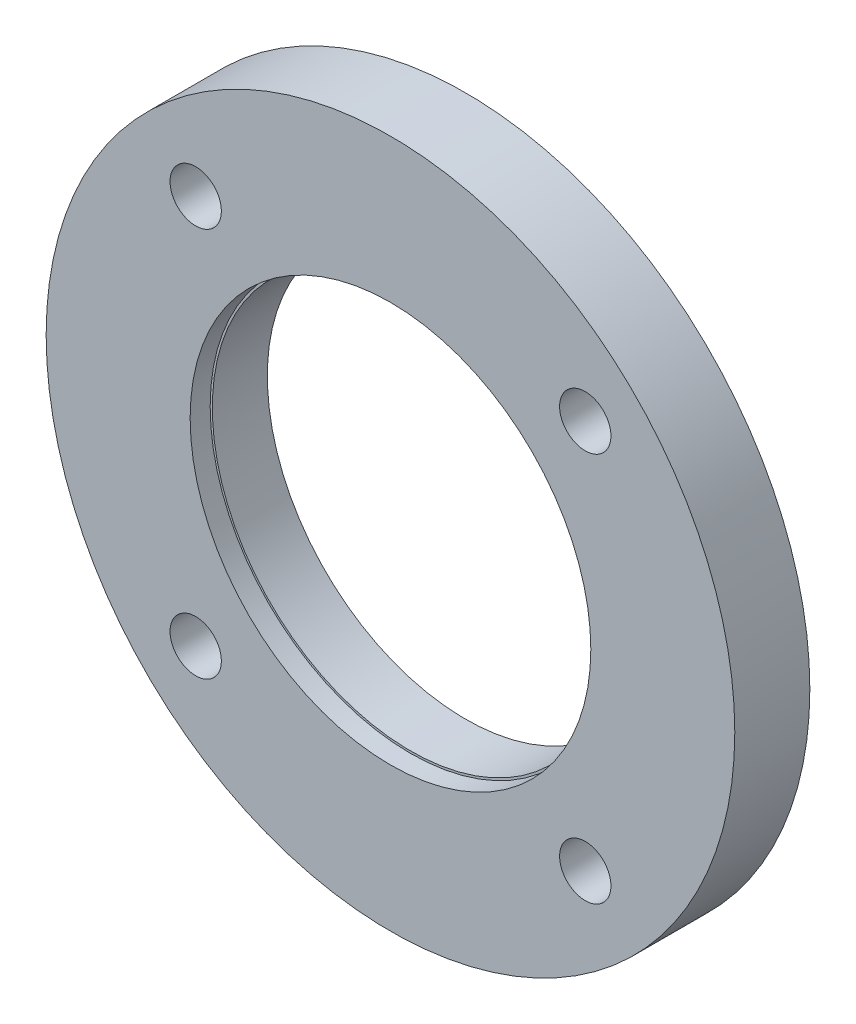
SolidWorks part; units mm, degrees
ref_plane "Front Plane" through (0, 0, 0) normal (0, 0, 1) x (1, 0, 0)
ref_plane "Top Plane" through (0, 0, 0) normal (0, 1, 0) x (1, 0, 0)
ref_plane "Right Plane" through (0, 0, 0) normal (1, 0, 0) x (0, 0, -1)
ref_axis "Z" through (0, 0, -0.1647) along (0, 0, 1)
sketch "Sketch1" plane through (0, 0, 0) normal (0, 1, 0) x (1, 0, 0)
  line L0 (-15.83, 0) -> (-27.5, 0)
  line L1 (-27.5, 0) -> (-27.5, -5.994)
  line L2 (-27.5, -5.994) -> (-16, -5.994)
  line L3 (-16, -5.994) -> (-16, -4.394)
  line L4 (-16, -4.394) -> (-15.83, -4.394)
  line L5 (-15.83, -4.394) -> (-15.83, 0)
  line L6 (0, -1.0245) -> (0, 4.9373) construction
  dimension "D1" = 1.6
  dimension "D2" = 32
  dimension "D3" = 0.17
  dimension "D4" = 4.394
  dimension "D5" = 55
revolve "Revolve1" add sketch "Sketch1" angle 360 about L6
sketch "Sketch2" plane through (0, 0, 0) normal (0, 0, 1) x (1, 0, 0)
  line L0 (-15.5563, 15.5563) -> (0, 0) construction
  line L1 (0, 0) -> (0, 34.6787) construction
  circle A0 centre (-15.5563, 15.5563) radius 2.05
  circle A1 centre (15.5563, 15.5563) radius 2.05
  circle A2 centre (15.5563, -15.5563) radius 2.05
  circle A3 centre (-15.5563, -15.5563) radius 2.05
  point P13 (0, 0)
  dimension "D4" = 4.1
  dimension "D1" = 22
  dimension "D3" = 45
  dimension "D2" = 4
extrude "Cut-Extrude1" cut sketch "Sketch2" along normal through all
